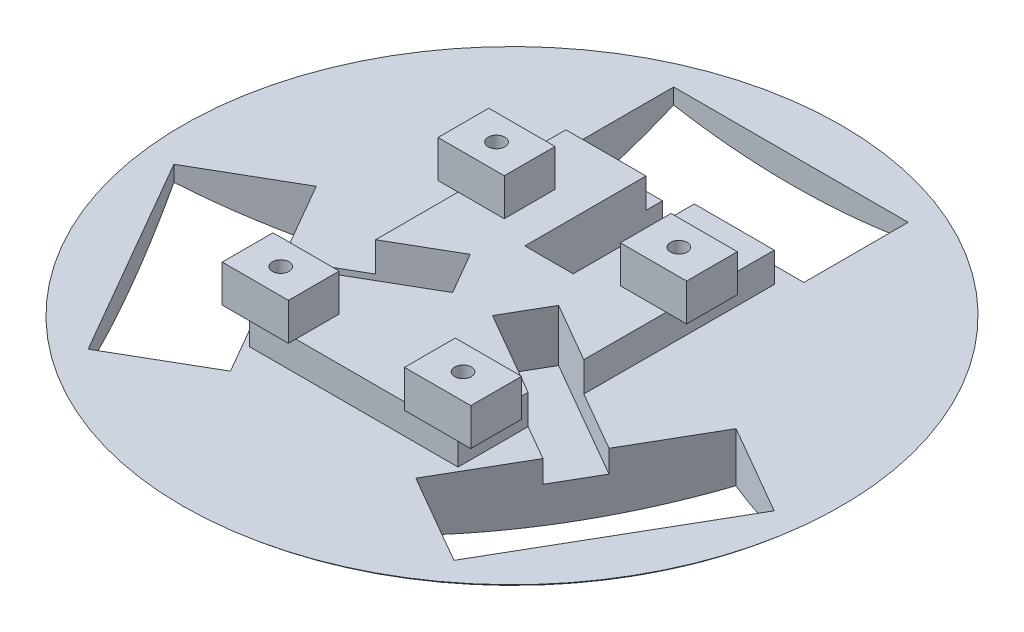
SolidWorks part; units mm, degrees
ref_plane "Front Plane" through (0, 0, 0) normal (0, 0, 1) x (1, 0, 0)
ref_plane "Top Plane" through (0, 0, 0) normal (0, 1, 0) x (1, 0, 0)
ref_plane "Right Plane" through (0, 0, 0) normal (1, 0, 0) x (0, 0, -1)
sketch "Sketch2" plane through (0, 0, 0) normal (0, 1, 0) x (1, 0, 0)
  line L0 (0, -68.0098) -> (0, 65.7503) construction
  line L1 (-31.5, 74.9495) -> (31.5, 74.9495)
  line L2 (-31.5, 74.9495) -> (-31.5, 46.9495)
  line L3 (-31.5, 46.9495) -> (31.5, 46.9495)
  line L4 (31.5, 74.9495) -> (31.5, 46.9495)
  line L5 (-31.5, 74.9495) -> (31.5, 46.9495) construction
  line L6 (-31.5, 46.9495) -> (31.5, 74.9495) construction
  line L7 (-70.2148, 0) -> (95.7201, 0) construction
  line L8 (0, 0) -> (-72.5813, -41.9048) construction
  line L9 (0, 0) -> (72.5813, -41.9048) construction
  line L10 (80.6581, -10.1949) -> (49.1581, -64.7545)
  line L11 (56.4094, 3.8051) -> (24.9094, -50.7545)
  line L12 (80.6581, -10.1949) -> (56.4094, 3.8051)
  line L13 (49.1581, -64.7545) -> (24.9094, -50.7545)
  line L14 (-49.1581, -64.7545) -> (-80.6581, -10.1949)
  line L15 (-24.9094, -50.7545) -> (-56.4094, 3.8051)
  line L16 (-49.1581, -64.7545) -> (-24.9094, -50.7545)
  line L17 (-80.6581, -10.1949) -> (-56.4094, 3.8051)
  line L18 (-6.5, -8.0505) -> (6.5, 46.9495) construction
  line L19 (-6.5, 46.9495) -> (6.5, 46.9495)
  line L20 (-6.5, 46.9495) -> (-6.5, -8.0505)
  line L21 (-6.5, -8.0505) -> (6.5, -8.0505)
  line L22 (6.5, 46.9495) -> (6.5, -8.0505)
  line L23 (-6.5, 46.9495) -> (6.5, -8.0505) construction
  line L24 (31.4023, -15.1408) -> (6.5, -0.7634)
  line L25 (-6.1216, -8.0505) -> (0, 2.5524)
  line L26 (24.9023, -26.3991) -> (0, -12.0218)
  line L27 (-25.0514, -26.4852) -> (0, -12.0218)
  line L28 (0, 2.5524) -> (6.1216, -8.0505)
  line L29 (-33.4324, -16.3129) -> (-6.5, -0.7634)
  circle A2 centre (0, 0) radius 16 construction
  point P3 (0, 19.4495)
  point P4 (0, 46.9495)
  point P6 (0, 60.9495)
  point P13 (0, 0)
  point P33 (0, 0)
  point P41 (0, -4.5162)
  dimension "D1" = 55
  dimension "D2" = 13
  dimension "D3" = 32
  dimension "D5" = 63
  dimension "D6" = 120
  dimension "D7" = 28
  dimension "D8" = 3
  dimension "D4" = 3
sketch "Sketch3" plane through (0, 0, 0) normal (1, 0, 0) x (0, 0, -1)
  line L0 (0, 83.7838) -> (0, -101.0811) construction
  line L1 (-115.9459, 0) -> (127.2973, 0) construction
  line L5 (0, 20) -> (0, 0)
  line L6 (88.569, 20) -> (0, 20)
  arc A3 (84.754, 17.3868) -> (0, 0) centre (7.3808, 179.2865) cw
  arc A4 (84.754, 17.3868) -> (88.569, 20) centre (78.286, 30.9207) ccw
  point P13 (90, 5.0684)
  dimension "D5" = 179.4384
  dimension "D1" = 15
  dimension "D2" = 20
  dimension "D3" = 20
  dimension "D4" = 90
revolve "Revolve1" add sketch "Sketch3" angle 360 about L5
extrude "Cut-Extrude1" cut sketch "Sketch2" along normal blind 40 contours L3 L4 L1 L2 | L15 L17 L14 L16 | L11 L13 L10 L12
sketch "Sketch4" plane through (0, 20, 0) normal (0, 1, 0) x (1, 0, 0)
  line L1 (-6.5, 46.9495) -> (6.5, 46.9495)
  line L2 (-6.5, 46.9495) -> (-6.5, 9.9495)
  line L3 (-6.5, 9.9495) -> (6.5, 9.9495)
  line L4 (6.5, 46.9495) -> (6.5, 9.9495)
  line L5 (-6.5, 46.9495) -> (6.5, 9.9495) construction
  line L6 (-6.5, 9.9495) -> (6.5, 46.9495) construction
  line L7 (43.9094, -17.8456) -> (37.4094, -29.1039)
  line L8 (-56.4094, 3.8051) -> (-24.9094, -50.7545) construction
  line L9 (-31.5, 46.9495) -> (31.5, 46.9495) construction
  line L10 (56.4094, 3.8051) -> (24.9094, -50.7545) construction
  line L26 (43.9094, -17.8456) -> (11.8665, 0.6544)
  line L27 (37.4094, -29.1039) -> (5.3665, -10.6039)
  line L28 (11.8665, 0.6544) -> (5.3665, -10.6039)
  line L29 (-37.4094, -29.1039) -> (-43.9094, -17.8456)
  line L30 (-37.4094, -29.1039) -> (-5.3665, -10.6039)
  line L31 (-43.9094, -17.8456) -> (-11.8665, 0.6544)
  line L32 (-5.3665, -10.6039) -> (-11.8665, 0.6544)
  line L33 (49.1581, -64.7545) -> (41.827, -60.5219)
  line L34 (49.1581, -64.7545) -> (24.9094, -50.7545) construction
  line L35 (49.1581, -64.7545) -> (80.6581, -10.1949)
  line L36 (80.6581, -10.1949) -> (73.327, -5.9623)
  line L37 (80.6581, -10.1949) -> (56.4094, 3.8051) construction
  circle A0 centre (0, 0) radius 88.569 construction
  circle A1 centre (0, 0) radius 73.569 construction
  arc A2 (41.827, -60.5219) -> (73.327, -5.9623) centre (0, 0) ccw
  circle A3 centre (0, 0) radius 81.2999
  point P0 (0, 28.4495)
  point P5 (0, 46.9495)
  point P22 (0, 0)
  point P23 (0, 4.0327)
  point P32 (-2.3282, 4.0326)
  line M8 (-56.4094, 3.8051) -> (-24.9094, -50.7545)
  line M13 (24.9094, -50.7545) -> (56.4094, 3.8051)
  line M17 (31.5, 46.9495) -> (-31.5, 46.9495)
  dimension "D4" = 177.1379
  dimension "D5" = 147.1379
  dimension "D6" = 162.5998
  dimension "D1" = 13
  dimension "D2" = 37
  dimension "D3" = 15
extrude "Cut-Extrude2" cut sketch "Sketch4" against normal blind 6 contours L4 L2 L3 M17 | L30 L32 L31 M8 | L26 L28 L27 M13 region at (0, 20, -28.4495) region at (24.638, 20, 14.2247) region at (-24.638, 20, 14.2247)
sketch "Sketch5" plane through (0, 20, 0) normal (0, 1, 0) x (1, 0, 0)
  line L1 (-28, 42.5) -> (-6.5, 42.5)
  line L2 (-28, 42.5) -> (-28, -8.6603)
  line L3 (-28, -42.5) -> (28, -42.5)
  line L5 (-28, 42.5) -> (28, -42.5) construction
  line L6 (-28, -42.5) -> (28, 42.5) construction
  line L7 (-37.4094, -29.1039) -> (-5.3665, -10.6039) construction
  line L10 (-43.9094, -17.8456) -> (-11.8665, 0.6544) construction
  line L12 (37.4094, -29.1039) -> (5.3665, -10.6039) construction
  line L18 (6.5, 46.9495) -> (6.5, 9.9495) construction
  line L19 (6.5, 46.9495) -> (6.5, 9.9495) construction
  line L20 (-28, -23.6714) -> (-28, -42.5)
  line L21 (28, -23.6714) -> (28, -42.5)
  line L22 (6.5, 42.5) -> (28, 42.5)
  line L23 (0, 13.9495) -> (0, -42.8187) construction
  line L24 (28, 42.5) -> (27.888, -8.5956)
  line L26 (-6.5, 46.9495) -> (-6.5, 9.9495) construction
  line L27 (43.9094, -17.8456) -> (11.8665, 0.6544) construction
  line L28 (27.888, -8.5956) -> (11.8665, 0.6544)
  line L29 (11.8665, 0.6544) -> (5.3665, -10.6039)
  line L30 (-28, -8.6603) -> (-11.8665, 0.6544)
  line L31 (-11.8665, 0.6544) -> (-5.3665, -10.6039)
  line L32 (-6.5, 42.5) -> (-6.5, 9.9495)
  line L33 (-6.5, 9.9495) -> (6.5, 9.9495)
  line L34 (-5.3665, -10.6039) -> (-28, -23.6714)
  line L35 (5.3665, -10.6039) -> (28, -23.6714)
  line L36 (6.5, 9.9495) -> (6.5, 42.5)
  line L40 (0, -51.0669) -> (0, 44.2573) construction
  line L41 (-47.7731, 0) -> (43.2855, 0) construction
  circle A0 centre (-24.5, -37.6603) radius 2.25
  circle A1 centre (24.5, -37.6603) radius 2.25
  circle A2 centre (24.5, 20.3397) radius 2.25
  circle A3 centre (-24.5, 20.3397) radius 2.25
  point P0 (0, 0)
  point P56 (0, 0)
  dimension "D1" = 56
  dimension "D2" = 85
  dimension "D4" = 49
  dimension "D5" = 58
extrude "Boss-Extrude1" add sketch "Sketch5" along normal blind 8
sketch "Sketch6" plane through (0, 28, 0) normal (0, 1, 0) x (1, 0, 0)
  line L0 (-15.5977, 13.519) -> (-15.5977, 27.1605)
  line L1 (-15.5977, 27.1605) -> (-33.4023, 27.1605)
  line L2 (-33.4023, 27.1605) -> (-33.4023, 13.519)
  line L3 (-33.4023, 13.519) -> (-15.5977, 13.519)
  line L4 (-33.4023, 27.1605) -> (-15.5977, 13.519) construction
  line L5 (-33.4023, 13.519) -> (-15.5977, 27.1605) construction
  line L6 (0, -54.2519) -> (0, 64.1127) construction
  line L7 (-44.9076, -8.6603) -> (39.6765, -8.6603) construction
  line L8 (33.4023, 13.519) -> (15.5977, 13.519)
  line L9 (15.5977, 13.519) -> (15.5977, 27.1605)
  line L10 (15.5977, 27.1605) -> (33.4023, 27.1605)
  line L11 (33.4023, 27.1605) -> (33.4023, 13.519)
  line L12 (15.5977, -30.8395) -> (15.5977, -44.481)
  line L13 (33.4023, -30.8395) -> (15.5977, -30.8395)
  line L14 (33.4023, -44.481) -> (33.4023, -30.8395)
  line L15 (15.5977, -44.481) -> (33.4023, -44.481)
  line L16 (-33.4023, -44.481) -> (-33.4023, -30.8395)
  line L17 (-33.4023, -30.8395) -> (-15.5977, -30.8395)
  line L18 (-15.5977, -30.8395) -> (-15.5977, -44.481)
  line L19 (-15.5977, -44.481) -> (-33.4023, -44.481)
  circle A0 centre (-24.5, 20.3397) radius 2.25
  circle A1 centre (-24.5, -37.6603) radius 2.25
  circle A2 centre (24.5, 20.3397) radius 2.25
  circle A3 centre (24.5, -37.6603) radius 2.25
  point P7 (-24.5, 20.3397)
  point P26 (0, 0)
  dimension "D1" = 29
  dimension "D2" = 29
  dimension "D3" = 58
extrude "Boss-Extrude2" add sketch "Sketch6" along normal blind 10
